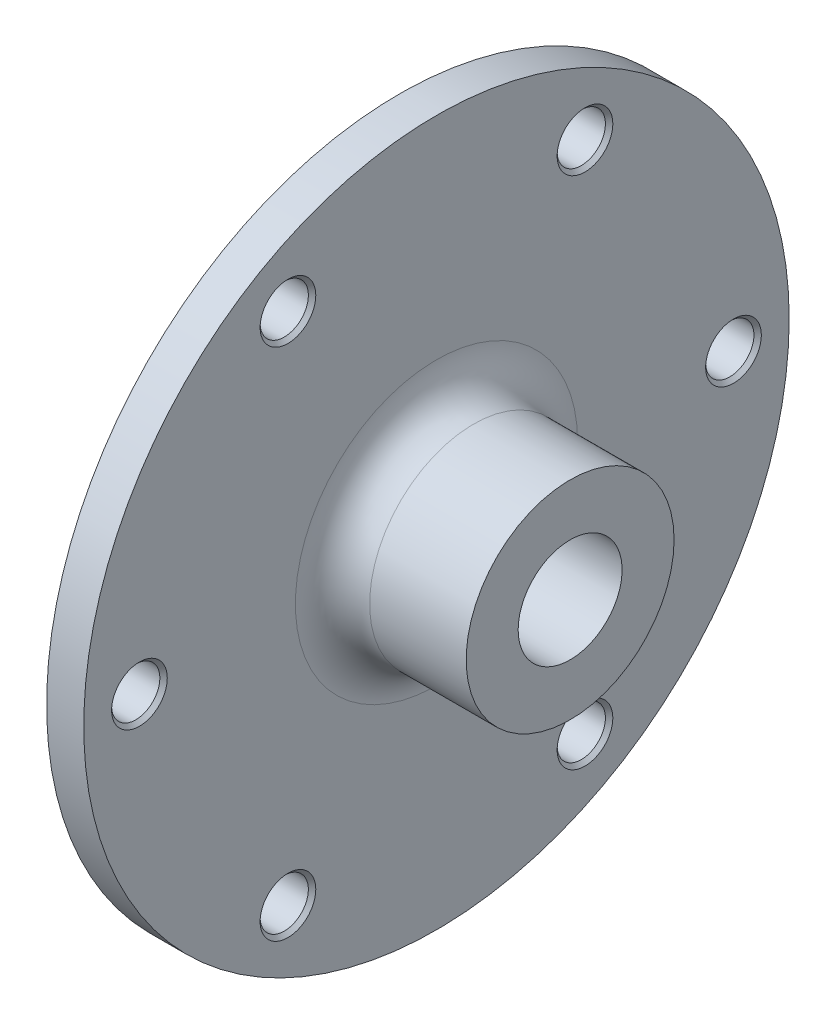
SolidWorks part; units mm, degrees
ref_plane "Front Plane" through (0, 0, 0) normal (0, 0, 1) x (1, 0, 0)
ref_plane "Top Plane" through (0, 0, 0) normal (0, 1, 0) x (1, 0, 0)
ref_plane "Right Plane" through (0, 0, 0) normal (1, 0, 0) x (0, 0, -1)
sketch "Sketch1" plane through (0, 0, 0) normal (0, 0, 1) x (1, 0, 0)
  line L0 (0, 0) -> (-28, 0)
  line L1 (-28, 0) -> (-28, 35)
  line L2 (-28, 35) -> (-23, 35)
  line L3 (-23, 35) -> (-23, 47.5)
  line L4 (-23, 47.5) -> (-18, 47.5)
  line L5 (-18, 47.5) -> (-18, 14)
  line L6 (-18, 14) -> (0, 14)
  line L7 (0, 14) -> (0, 0)
  dimension "D1" = 28
  dimension "D2" = 14
  dimension "D3" = 47.5
  dimension "D4" = 35
  dimension "D5" = 5
  dimension "D6" = 5
revolve "Revolve1" add sketch "Sketch1" angle 360 about L0
fillet "Fillet1" radius 5 1 edges at (-18, 0, -14)
hole_wizard "CSK for M12 Hex Socket Countersunk Cap Screw1" positions "Sketch2" profile "Sketch3" countersink size "M12" standard "ISO" end condition through all
sketch "Sketch2" plane through (-28, 0, 0) normal (-1, 0, 0) x (0, 0, 1)
  point P0 (0, 0)
sketch "Sketch3" plane through (-28, 0, 0) normal (0, 1, 0) x (0, 0, 1)
  line L0 (0, 0) -> (0, 28)
  line L1 (0, 28) -> (7, 28)
  line L2 (7, 28) -> (7, 6)
  line L3 (7, 6) -> (13, 0)
  line L5 (13, 0) -> (0, 0)
  line L6 (-7, 6) -> (-13, 0) construction
  line L11 (0, -6.35) -> (0, 107.95) construction
  dimension "Thru Hole Dia." = 14
  dimension "Thru Hole Depth" = 28
  dimension "Near C'Sink Dia." = 26
  dimension "Near C'Sink Angle" = 90
sketch "Sketch4" plane through (-18, 0, 0) normal (1, 0, 0) x (0, 0, -1)
  circle A0 centre (0, 0) radius 40 construction
  dimension "D1" = 80
hole_wizard "CSK for M6 Hex Socket Countersunk Cap Screw1" positions "Sketch5" profile "Sketch6" countersink size "M6" standard "ISO" end condition through all
sketch "Sketch5" plane through (-18, 0, 0) normal (1, 0, 0) x (0, 0, -1)
  circle A0 centre (0, 0) radius 40 construction
  point P0 (-40, 0)
sketch "Sketch6" plane through (-18, 0, 40) normal (0, 1, 0) x (0, 0, -1)
  line L0 (0, 0) -> (0, 10)
  line L1 (0, 10) -> (3.25, 10)
  line L2 (3.25, 10) -> (3.25, 0.5)
  line L3 (3.25, 0.5) -> (3.75, 0)
  line L5 (3.75, 0) -> (0, 0)
  line L6 (-3.25, 0.5) -> (-3.75, 0) construction
  line L11 (0, -6.35) -> (0, 107.95) construction
  dimension "Thru Hole Dia." = 6.5
  dimension "Thru Hole Depth" = 10
  dimension "Near C'Sink Dia." = 7.5
  dimension "Near C'Sink Angle" = 90
pattern_circular "CirPattern1" count 6 over 360 about axis through (0, 0, 0) along (1, 0, 0) of "CSK for M6 Hex Socket Countersunk Cap Screw1"
